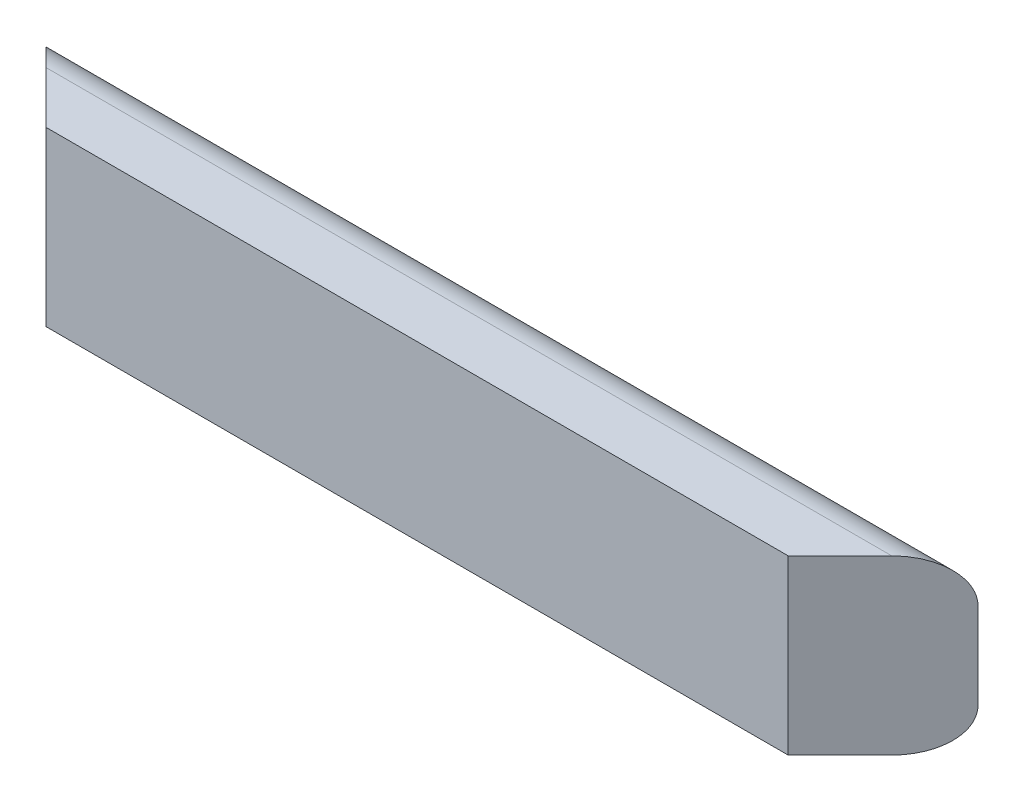
SolidWorks part; units mm, degrees
ref_plane "Front Plane" through (0, 0, 0) normal (0, 0, 1) x (1, 0, 0)
ref_plane "Top Plane" through (0, 0, 0) normal (0, 1, 0) x (1, 0, 0)
ref_plane "Right Plane" through (0, 0, 0) normal (1, 0, 0) x (0, 0, -1)
sketch "Sketch1" plane through (0, 0, 0) normal (1, 0, 0) x (0, 0, -1)
  line L0 (6.35, 127) -> (38.1, 127)
  line L1 (0, 0) -> (6.35, 0)
  line L2 (0, 0) -> (0, 127)
  line L3 (0, 127) -> (6.35, 127)
  line L5 (69.85, 95.25) -> (69.85, 31.75)
  line L6 (38.1, 0) -> (6.35, 0)
  arc A0 (69.85, 95.25) -> (38.1, 127) centre (38.1, 95.25) ccw
  arc A1 (38.1, 0) -> (69.85, 31.75) centre (38.1, 31.75) ccw
  dimension "D3" = 63.5
  dimension "D5" = 31.75
  dimension "D1" = 127
  dimension "D2" = 6.35
  dimension "D4" = 31.75
extrude "Boss-Extrude1" add sketch "Sketch1" along normal blind 342.9 and the other way blind 342.9
sketch "Sketch2" plane through (0, 127, 0) normal (0, 1, 0) x (1, 0, 0)
  line L0 (342.9, 69.85) -> (273.05, 0)
  line L1 (-55, 0) -> (55, 0) construction
  line L2 (-342.9, 69.85) -> (-273.05, 0)
  line L3 (-342.9, 69.85) -> (-342.9, 0)
  line L4 (-342.9, 38.1) -> (-342.9, 0) construction
  line L5 (-342.9, 0) -> (-273.05, 0)
  line L6 (342.9, 69.85) -> (342.9, 0)
  line L7 (342.9, 38.1) -> (342.9, 0) construction
  line L8 (342.9, 0) -> (273.05, 0)
  dimension "D1" = 45
  dimension "D2" = 45
extrude "Cut-Extrude1" cut sketch "Sketch2" against normal through all
sketch "Sketch3" plane through (0, 0, -69.85) normal (0, 0, -1) x (-1, 0, 0)
  line L0 (0, 38.5572) -> (0, -38.5572) construction
  line L1 (38.5572, 0) -> (-38.5572, 0) construction
  text T0 "3597" font "Arial" height in points 200
  dimension "D1" = 114.3
  dimension "D2" = 38.1
